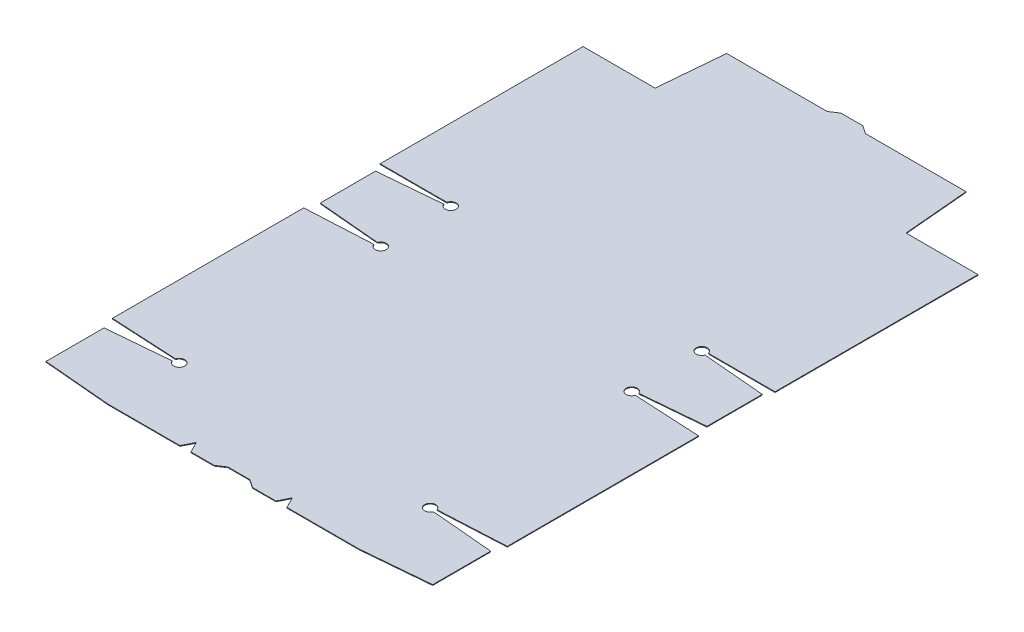
SolidWorks part; units mm, degrees
material "CHIP BOARD"
ref_plane "Front Plane" through (0, 0, 0) normal (0, 0, 1) x (1, 0, 0)
ref_plane "Top Plane" through (0, 0, 0) normal (0, 1, 0) x (1, 0, 0)
ref_plane "Right Plane" through (0, 0, 0) normal (1, 0, 0) x (0, 0, -1)
sketch "Sketch1" plane through (0, 0, 0) normal (0, 1, 0) x (1, 0, 0)
  line L0 (145.2563, 434.1812) -> (138.0341, 516.7312)
  line L1 (-146.05, 116.6812) -> (146.05, 116.6812) construction
  line L3 (145.2562, -199.2313) -> (223.8375, -192.3563)
  line L5 (-146.05, -116.6813) -> (146.05, -116.6813) construction
  line L6 (228.6, 434.1812) -> (228.6, 199.2312) construction
  line L7 (-145.2562, -199.2313) -> (145.2562, -199.2313)
  line L8 (146.05, 199.2312) -> (146.05, 116.6812) construction
  line L9 (-145.2562, -199.2313) -> (-223.8375, -192.3563)
  line L10 (228.6, -110.7237) -> (145.1732, -115.0959)
  line L11 (-228.6, -110.7237) -> (-145.1732, -115.0959)
  line L12 (-228.6, -110.7237) -> (-228.6, 110.7237)
  line L14 (223.8375, -192.3563) -> (223.8375, -125.1498)
  line L15 (223.8375, -125.1498) -> (145.1179, -118.2627)
  line L16 (-138.0341, 516.7312) -> (-145.2563, 434.1812)
  line L18 (145.2563, 434.1812) -> (228.6, 434.1812)
  line L19 (145.1179, 196.0623) -> (223.8375, 189.1752)
  line L21 (228.6, -110.7237) -> (228.6, 110.7237)
  line L22 (-145.2563, 434.1812) -> (-228.6, 434.1812)
  line L23 (228.6, 199.2312) -> (145.2562, 199.2312)
  line L24 (-228.6, 110.7237) -> (-145.1732, 115.0959)
  line L25 (223.8375, 189.1752) -> (223.8375, 125.1498)
  line L26 (228.6, 110.7237) -> (145.1732, 115.0959)
  line L27 (223.8375, 125.1498) -> (145.1179, 118.2627)
  line L28 (-228.6, 199.2312) -> (-145.2562, 199.2312)
  line L29 (0, 0) -> (0, 116.6812) construction
  line L32 (-145.1179, 196.0623) -> (-223.8375, 189.1752)
  line L33 (146.05, 116.6812) -> (146.05, -116.6813) construction
  line L34 (-146.05, 199.2312) -> (228.6, 199.2312) construction
  line L35 (145.2562, -116.6813) -> (145.2562, -199.2313) construction
  line L36 (-145.2562, -199.2313) -> (-145.2562, -116.6813) construction
  line L37 (-223.8375, 189.1752) -> (-223.8375, 125.1498)
  line L38 (-223.8375, 125.1498) -> (-145.1179, 118.2627)
  line L39 (228.6, 199.2312) -> (228.6, 434.1812)
  line L40 (-146.05, -116.6813) -> (-146.05, 116.6812) construction
  line L41 (-146.05, 116.6812) -> (-146.05, 199.2312) construction
  line L42 (-228.6, 434.1812) -> (-228.6, 199.2312) construction
  line L43 (-228.6, 434.1812) -> (228.6, 434.1812) construction
  line L44 (-138.0341, 516.7312) -> (138.0341, 516.7312)
  line L45 (0, 0) -> (-146.05, 0) construction
  line L48 (-228.6, 434.1812) -> (-228.6, 199.2312)
  line L49 (-223.8375, -192.3563) -> (-223.8375, -125.1498)
  line L50 (-223.8375, -125.1498) -> (-145.1179, -118.2627)
  arc A0 (-145.1179, -118.2627) -> (-145.1732, -115.0959) centre (-145.2562, -116.6813) ccw
  arc A1 (145.1732, -115.0959) -> (145.1179, -118.2627) centre (145.2562, -116.6813) ccw
  arc A2 (145.1179, 118.2627) -> (145.1732, 115.0959) centre (145.2562, 116.6812) ccw
  arc A3 (-145.1732, 115.0959) -> (-145.1179, 118.2627) centre (-145.2562, 116.6812) ccw
  arc A4 (-145.1179, 196.0623) -> (-145.2562, 199.2312) centre (-145.2562, 197.6437) ccw
  arc A5 (145.2562, 199.2312) -> (145.1179, 196.0623) centre (145.2562, 197.6437) ccw
  point P4 (0, 116.6812)
  dimension "D5" = 1.5875
  dimension "E1" = 82.55
  dimension "E2" = 82.55
  dimension "D7" = 5
  dimension "A1" = 233.3625
  dimension "A2" = 234.95
  dimension "E3" = 82.55
  dimension "C1" = 292.1
  dimension "C2" = 292.1
  dimension "D19" = 95
  dimension "E4" = 82.55
  dimension "B1" = 447.675
  dimension "D6" = 93
  dimension "D15" = 93
  dimension "D18" = 93
  dimension "D10" = 95
  dimension "D14" = 95
  dimension "D21" = 95
  dimension "D16" = 0.7937
extrude "Extrude1" add sketch "Sketch1" along normal blind 0.7937
sketch "Sketch2" plane through (0, 0.7937, 0) normal (0, 1, 0) x (1, 0, 0)
  circle A0 centre (-145.2562, 116.6812) radius 6.35
  circle A1 centre (-145.2562, -116.6813) radius 6.35
  circle A2 centre (145.2562, -116.6813) radius 6.35
  circle A3 centre (145.2562, 116.6812) radius 6.35
  circle A4 centre (-145.2562, 197.6437) radius 6.35
  circle A5 centre (145.2562, 197.6437) radius 6.35
  arc A6 (145.1732, -115.0959) -> (145.1179, -118.2627) centre (145.2562, -116.6813) ccw construction
  arc A7 (-145.1179, 196.0623) -> (-145.2562, 199.2312) centre (-145.2562, 197.6437) ccw construction
  arc A8 (-145.1732, 115.0959) -> (-145.1179, 118.2627) centre (-145.2562, 116.6812) ccw construction
  arc A9 (-145.1179, -118.2627) -> (-145.1732, -115.0959) centre (-145.2562, -116.6813) ccw construction
  arc A10 (145.1179, 118.2627) -> (145.1732, 115.0959) centre (145.2562, 116.6812) ccw construction
  arc A11 (145.2562, 199.2312) -> (145.1179, 196.0623) centre (145.2562, 197.6437) ccw construction
  dimension "D1" = 12.7
extrude "Extrude2" cut sketch "Sketch2" against normal up to next
sketch "Sketch12" plane through (0, 0.7937, 0) normal (0, 1, 0) x (1, 0, 0)
  line L0 (-138.5896, 510.3813) -> (-22.225, 510.3813)
  line L1 (-138.0341, 516.7312) -> (-145.2563, 434.1812) construction
  line L2 (-22.225, 510.3813) -> (-12.7, 516.7312)
  line L3 (138.0341, 516.7312) -> (-138.0341, 516.7312) construction
  line L4 (12.7, 516.7312) -> (22.225, 510.3813)
  line L5 (22.225, 510.3813) -> (138.5896, 510.3813)
  line L6 (145.2563, 434.1812) -> (138.0341, 516.7312) construction
  line L7 (138.5896, 510.3813) -> (138.0341, 516.7312)
  line L8 (138.0341, 516.7312) -> (12.7, 516.7312)
  line L9 (-12.7, 516.7312) -> (-138.0341, 516.7312)
  line L10 (-138.0341, 516.7312) -> (-138.5896, 510.3813)
  dimension "D1" = 6.35
  dimension "D2" = 25.4
  dimension "D3" = 44.45
extrude "Extrude3" cut sketch "Sketch12" against normal up to next
sketch "Sketch13" plane through (0, 0.7937, 0) normal (0, 1, 0) x (1, 0, 0)
  line L0 (-61.9125, -199.2313) -> (-55.5625, -186.5313)
  line L1 (-145.2562, -199.2313) -> (145.2562, -199.2313) construction
  line L2 (-55.5625, -186.5313) -> (-49.2125, -199.2313)
  line L3 (-49.2125, -199.2313) -> (-61.9125, -199.2313)
  line L4 (49.2125, -199.2313) -> (55.5625, -186.5313)
  line L5 (55.5625, -186.5313) -> (61.9125, -199.2313)
  line L6 (49.2125, -199.2313) -> (61.9125, -199.2313)
  line L7 (-55.5625, -186.5313) -> (55.5625, -186.5313) construction
  line L8 (-55.5625, -186.5313) -> (-55.5625, -199.2313) construction
  line L9 (55.5625, -186.5313) -> (55.5625, -199.2313) construction
  line L10 (-22.225, -199.2313) -> (-12.7, -192.8813)
  line L11 (-12.7, -192.8813) -> (12.7, -192.8813)
  line L12 (12.7, -192.8813) -> (22.225, -199.2313)
  line L13 (22.225, -199.2313) -> (-22.225, -199.2313)
  point P7 (0, -186.5313)
  point P14 (0, -192.8813)
  point P17 (0, -199.2313)
  dimension "D1" = 12.7
  dimension "D2" = 111.125
  dimension "D3" = 12.7
  dimension "D4" = 6.35
  dimension "D5" = 25.4
  dimension "D6" = 44.45
extrude "Extrude4" cut sketch "Sketch13" against normal up to next
sheet metal parameters "Sheet-Metal1" parameters "D1"=0.7937
flatten bends "Flatten-Bends1" parameters "D1"=0
sketch "Sharp-Sketch1" [suppressed] plane through (0, 0.7937, 0) normal (0, 1, 0) x (-1, 0, 0)
process bends "Process-Bends1" [suppressed] parameters "D1"=0
sketch "Flat-Sketch1" [suppressed] plane through (0, 0.7937, 0) normal (0, 1, 0) x (-1, 0, 0)
sketch "Sketch3" [suppressed] plane through (0, 0.7937, 0) normal (0, 1, 0) x (1, 0, 0)
  line L0 (-146.05, -122.9814) -> (-146.05, -199.2313)
  line L2 (-145.2562, -199.2313) -> (-61.9125, -199.2313) construction
  line L5 (-146.05, -199.2313) -> (146.05, -199.2313) construction
  line L6 (146.05, -122.9814) -> (146.05, -199.2313)
  arc A0 (151.3131, -114.7741) -> (151.2429, -118.7986) centre (145.2562, -116.6813) ccw construction
  arc A1 (-151.2429, -118.7986) -> (-151.3131, -114.7741) centre (-145.2562, -116.6813) ccw construction
  point P2 (0, -199.2313)
  dimension "D1" = 292.1
sketched bend "Sketched Bend10" [suppressed] parameters "D1"=0.7937
bend "SketchBend19" [suppressed] bend radius 0.7937 bend angle 90 parameters "D5"=7
bend "SketchBend20" [suppressed] bend radius 0 bend angle 90 parameters "D5"=8
sketch "Sketch7" [suppressed] plane through (0, 0.7937, 0) normal (0, 1, 0) x (1, 0, 0)
  line L0 (-146.8438, 110.5329) -> (-146.8438, -110.5329)
  line L1 (146.8438, 110.5329) -> (146.8438, -110.5329)
  line L2 (-146.8438, -110.5329) -> (146.8438, -110.5329) construction
  arc A0 (-151.3131, 114.7741) -> (-151.2429, 118.7986) centre (-145.2562, 116.6812) ccw construction
  arc A1 (151.3131, -114.7741) -> (145.2084, -123.0311) centre (145.2562, -116.6813) ccw construction
  arc A2 (-145.2084, -123.0311) -> (-151.3131, -114.7741) centre (-145.2562, -116.6813) ccw construction
  arc A4 (151.2429, 118.7986) -> (151.3131, 114.7741) centre (145.2562, 116.6812) ccw construction
  point P5 (0, -110.5329)
  dimension "D1" = 293.6875
sketch "Sketch11" [suppressed] plane through (0, 0.7937, 0) normal (0, 1, 0) x (1, 0, 0)
  line L0 (-146.05, 191.3436) -> (-146.05, 122.9814)
  line L1 (146.05, 191.3436) -> (146.05, 122.9814)
  line L2 (-146.05, 122.9814) -> (146.05, 122.9814) construction
  arc A0 (-151.2429, 195.5264) -> (-151.4046, 199.2312) centre (-145.2562, 197.6437) ccw construction
  arc A2 (151.4046, 199.2312) -> (151.2429, 195.5264) centre (145.2562, 197.6437) ccw construction
  arc A4 (151.2429, 118.7986) -> (151.3131, 114.7741) centre (145.2562, 116.6812) ccw construction
  arc A5 (-151.3131, 114.7741) -> (-151.2429, 118.7986) centre (-145.2562, 116.6812) ccw construction
  point P16 (0, 122.9814)
  dimension "D1" = 292.1
sketched bend "Sketched Bend9" [suppressed] parameters "D1"=0
bend "SketchBend17" [suppressed] bend radius 0.7937 bend angle 90 parameters "D5"=5
bend "SketchBend18" [suppressed] bend radius 0 bend angle 90 parameters "D5"=6
sketch "Sketch8" [suppressed] plane through (0, 0.7937, 0) normal (0, 1, 0) x (1, 0, 0)
  line L0 (-151.6062, 116.6813) -> (151.6062, 116.6813)
  line L1 (138.9063, -116.6813) -> (-138.9062, -116.6813)
  line L3 (0, 116.6812) -> (0, -116.6812) construction
  arc A2 (-145.2084, -123.0311) -> (-151.3131, -114.7741) centre (-145.2562, -116.6813) ccw construction
  circle A3 centre (145.2562, -116.6813) radius 6.35 construction
  arc A5 (-151.3131, 114.7741) -> (-145.2084, 123.0311) centre (-145.2562, 116.6812) ccw construction
  arc A7 (145.2084, 123.0311) -> (151.3131, 114.7741) centre (145.2562, 116.6812) ccw construction
  point P28 (0, 0)
  dimension "D1" = 233.3625
sketched bend "Sketched Bend5" [suppressed] parameters "D1"=1.5875
bend "SketchBend9" [suppressed] bend radius 1.5875 bend angle 90 parameters "D5"=3
bend "SketchBend10" [suppressed] bend radius 1.5875 bend angle 90 parameters "D5"=4
sketched bend "Sketched Bend6" [suppressed] parameters "D1"=1.5875
bend "SketchBend11" [suppressed] bend radius 1.5875 bend angle 90 parameters "D5"=1
bend "SketchBend12" [suppressed] bend radius 1.5875 bend angle 90 parameters "D5"=2
flat pattern "Flat-Pattern1"
sketch "Bend-Lines1" [suppressed] plane through (0, 0.4572, 0) normal (0, 1, 0) x (-1, 0, 0)
sketch3d "Bounding-Box1" [suppressed]
  line L0 (383.3812, -274.6375, 0) -> (383.3812, 360.3625, 0) construction
  line L1 (-89.6938, -274.6375, 0) -> (-89.6938, 360.3625, 0) construction
  line L2 (383.3812, -274.6375, 0) -> (-89.6938, -274.6375, 0) construction
  line L3 (383.3812, 360.3625, 0) -> (-89.6938, 360.3625, 0) construction
bend of the flat pattern "Flatten-<SketchBend11>1"
bend of the flat pattern "Flatten-<SketchBend12>1"
bend of the flat pattern "Flatten-<SketchBend9>1"
bend of the flat pattern "Flatten-<SketchBend10>1"
bend of the flat pattern "Flatten-<SketchBend17>1"
bend of the flat pattern "Flatten-<SketchBend18>1"
bend of the flat pattern "Flatten-<SketchBend19>1"
bend of the flat pattern "Flatten-<SketchBend20>1"
equation "\"D1@Sketch3\"= \"C1@Sketch1\""
equation "\"D1@Sketch11\"= \"C1@Sketch1\""
equation "\"D1@Sketch8\"= \"A1@Sketch1\""
equation "\"D1@Sketch7\"= \"C1@Sketch1\" + 2 * \"Thickness\""
